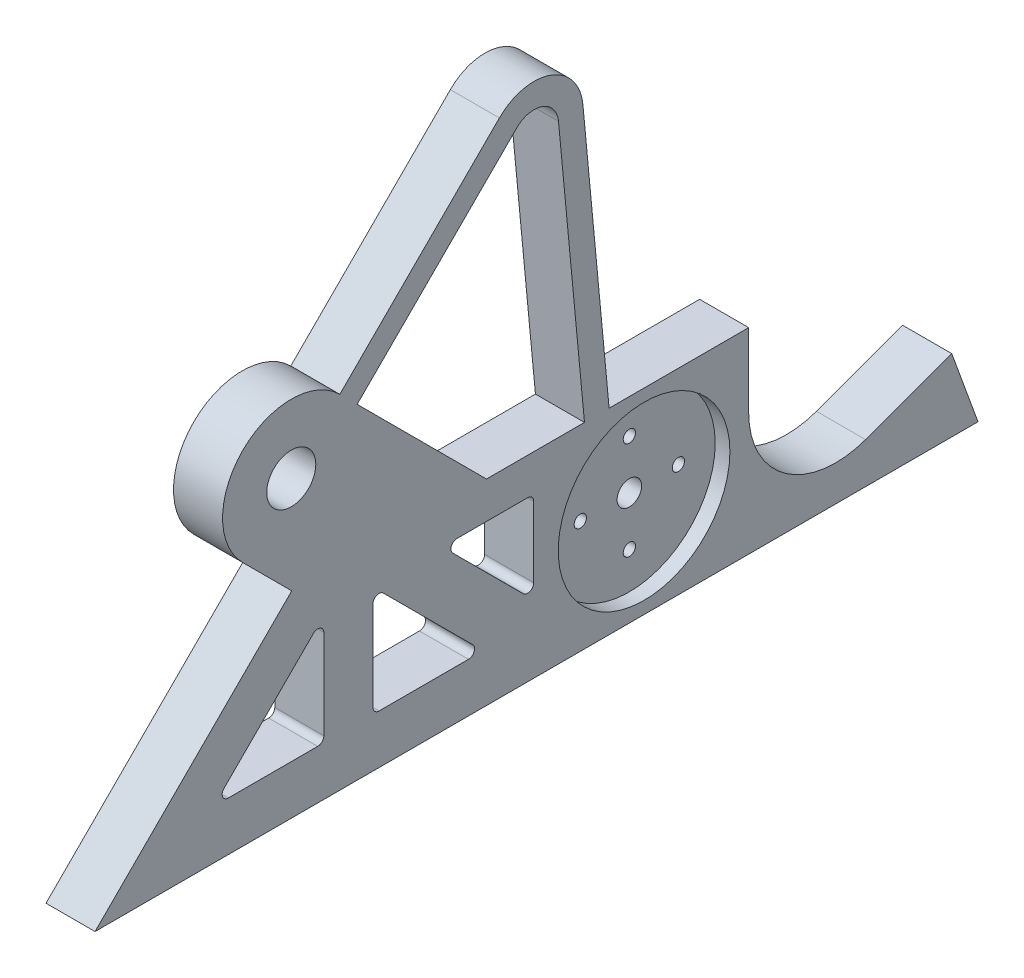
SolidWorks part; units mm, degrees
material "6061 Alloy"
ref_plane "Front Plane" through (0, 0, 0) normal (0, 0, 1) x (1, 0, 0)
ref_plane "Top Plane" through (0, 0, 0) normal (0, 1, 0) x (1, 0, 0)
ref_plane "Right Plane" through (0, 0, 0) normal (1, 0, 0) x (0, 0, -1)
sketch "Sketch1" plane through (0, 0, 0) normal (1, 0, 0) x (0, 0, -1)
  line L0 (114.3, 0) -> (-114.3, 0)
  line L1 (-114.3, 0) -> (-63.3724, 50.9276)
  line L2 (-63.3724, 50.9276) -> (-76.0724, 63.6276)
  line L3 (-50.9276, 88.7724) -> (-12.9553, 50.8)
  line L6 (114.3, 0) -> (95.8103, 50.8)
  line L8 (-12.9553, 50.8) -> (95.8103, 50.8)
  line L13 (85.18, 10.567) -> (107.4974, 18.6899)
  line L14 (54.9275, 31.75) -> (54.9275, 50.8)
  line L15 (-50.9276, 88.7724) -> (-9.6185, 130.0815)
  line L16 (18.7947, 50.8) -> (12.0049, 122.3019)
  line L17 (-46.4375, 84.2822) -> (-5.1283, 125.5914)
  line L18 (12.4732, 50.1997) -> (5.6834, 121.7016)
  arc A0 (-76.0724, 63.6276) -> (-50.9276, 88.7724) centre (-63.5, 76.2) cw
  circle A1 centre (-63.5, 76.2) radius 6.35
  circle A2 centre (77.47, 31.75) radius 22.5425
  arc A3 (-9.6185, 130.0815) -> (12.0049, 122.3019) centre (-0.6382, 121.1013) cw
  arc A4 (-5.1283, 125.5914) -> (5.6834, 121.7016) centre (-0.6382, 121.1013) cw
  point P4 (0, 0)
  dimension "D2" = 76.2
  dimension "D3" = 17.78
  dimension "D6" = 12.7
  dimension "D7" = 45.085
  dimension "D12" = 76.2
  dimension "D13" = 31.75
  dimension "D14" = 12.7
  dimension "D1" = 45
  dimension "D4" = 50.8
  dimension "D5" = 228.6
  dimension "D8" = 70
  dimension "D9" = 50.8
  dimension "D10" = 31.75
  dimension "D11" = 36.83
  dimension "D15" = 6.35
extrude "Boss-Extrude1" add sketch "Sketch1" along normal blind 12.7 contours A0 L2 L1 L0 L3 A1 | L17 A4 L18 L8 L16 A3 L15 L3 region at (0, 30.1646, 15.5647) region at (0, 108.6604, 29.5066)
sketch "Sketch3" plane through (12.7, 0, 0) normal (1, 0, 0) x (0, 0, -1)
  line L1 (-12.9553, 50.8) -> (12.4162, 50.8) construction
  circle A0 centre (27.8455, 25.4) radius 22.225
  circle A1 centre (27.8455, 25.4) radius 3.175
  arc A2 (54.9275, 31.75) -> (85.18, 10.567) centre (77.47, 31.75) ccw construction
  arc A3 (54.9275, 31.75) -> (85.18, 10.567) centre (77.47, 31.75) ccw
  circle A4 centre (27.8455, 38.1) radius 1.5875
  circle A5 centre (40.5455, 25.4) radius 1.5875
  circle A6 centre (27.8455, 12.7) radius 1.5875
  circle A7 centre (15.1455, 25.4) radius 1.5875
  circle A8 centre (27.8455, 38.1) radius 3.175
  circle A9 centre (40.5455, 25.4) radius 3.175
  circle A10 centre (27.8455, 12.7) radius 3.175
  circle A11 centre (15.1455, 25.4) radius 3.175
  circle A12 centre (-63.5, 76.2) radius 6.35 construction
  point P20 (27.8455, 25.4)
  point P29 (27.8455, 25.4)
  dimension "D1" = 44.45
  dimension "D2" = 25.4
  dimension "D4" = 3.175
  dimension "D7" = 6.35
  dimension "D8" = 6.35
  dimension "D3" = 104.521
  dimension "D5" = 12.7
  dimension "D6" = 4
  dimension "D9" = 4
extrude "Cut-Extrude1" cut sketch "Sketch3" against normal blind 3.81 contours A0 A7 A6 A5 A4 A1 | A11 A7 | A8 A4 | A9 A5 | A10 A6 region at (12.7, 25.4, -6.2491) region at (12.7, 38.1, -24.7603) region at (12.7, 25.4, -37.4603) region at (12.7, 12.7, -24.7603) region at (12.7, 25.4, -12.0603)
extrude "Cut-Extrude2" cut sketch "Sketch3<4>" against normal through all contours A1 | A7 | A4 | A5 | A6 region at (12.7, 25.4, -27.8455) region at (12.7, 38.1, -27.8455) region at (12.7, 25.4, -40.5455) region at (12.7, 12.7, -27.8455) region at (12.7, 25.4, -15.1455)
sketch "Sketch3<4>" plane through (12.7, 0, 0) normal (1, 0, 0) x (0, 0, -1) same geometry as "Sketch3"
extrude "Cut-Extrude3" cut sketch "Sketch3<5>" along normal blind 5.08 from surface contours A9 A5 | A8 A4 | A11 A7 | A10 A6 region at (12.7, 38.1, -24.7603) region at (12.7, 25.4, -37.4603) region at (12.7, 12.7, -24.7603) region at (12.7, 25.4, -12.0603) starting at face at (0, 25.4, -16.733)
sketch "Sketch3<5>" plane through (12.7, 0, 0) normal (1, 0, 0) x (0, 0, -1) same geometry as "Sketch3"
sketch "Sketch4" plane through (12.7, 0, 0) normal (1, 0, 0) x (0, 0, -1)
  line L0 (-83.6395, 12.7) -> (-55.0645, 41.275)
  line L1 (-55.0645, 41.275) -> (-55.0645, 12.7)
  line L2 (-55.0645, 12.7) -> (-83.6395, 12.7)
  line L3 (-42.3645, 41.275) -> (-42.3645, 12.7)
  line L4 (-42.3645, 12.7) -> (-13.7895, 12.7)
  line L5 (-13.7895, 12.7) -> (-42.3645, 41.275)
  line L6 (-24.404, 41.275) -> (-0.7295, 41.275)
  line L7 (-0.7295, 41.275) -> (-0.7295, 17.6005)
  line L8 (-0.7295, 17.6005) -> (-24.404, 41.275)
  line L9 (-114.3, 0) -> (-63.3724, 50.9276) construction
  line L10 (114.3, 0) -> (-114.3, 0) construction
  line L11 (-12.9553, 50.8) -> (12.4162, 50.8) construction
  circle A0 centre (27.8455, 25.4) radius 22.225 construction
  dimension "D3" = 12.7
  dimension "D1" = 12.7
  dimension "D2" = 28.575
  dimension "D4" = 12.7
  dimension "D5" = 12.7
  dimension "D6" = 9.525
extrude "Cut-Extrude4" cut sketch "Sketch4" against normal up to next
fillet "Fillet1" radius 1.5875 9 edges at (6.35, 12.7, 42.3645) (6.35, 12.7, 83.6395) (6.35, 12.7, 13.7895) (6.35, 12.7, 55.0645) (6.35, 17.6005, 0.7295) (6.35, 41.275, 0.7295) (6.35, 41.275, 24.404) (6.35, 41.275, 42.3645) (6.35, 41.275, 55.0645)
